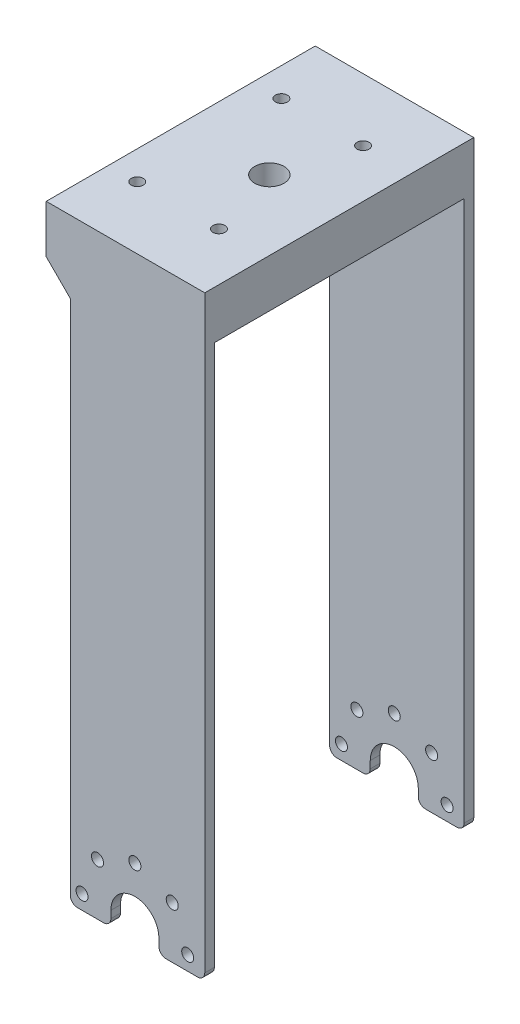
SolidWorks part; units mm, degrees
ref_plane "Front Plane" through (0, 0, 0) normal (0, 0, 1) x (1, 0, 0)
ref_plane "Top Plane" through (0, 0, 0) normal (0, 1, 0) x (1, 0, 0)
ref_plane "Right Plane" through (0, 0, 0) normal (1, 0, 0) x (0, 0, -1)
sketch "Sketch1" plane through (0, 0, 0) normal (0, 0, 1) x (1, 0, 0)
  line L1 (0, 0) -> (28, 0)
  line L2 (0, 0) -> (0, 124.1)
  line L3 (0, 124.1) -> (28, 124.1)
  line L4 (28, 0) -> (28, 124.1)
  dimension "D1" = 28
  dimension "D2" = 124.1
extrude "Boss-Extrude1" add sketch "Sketch1" against normal blind 2
ref_plane "Plane1" through (0, 0, -56) normal (0, 0, 1) x (1, 0, 0)
sketch "Sketch3" plane through (0, 0, 0) normal (0, 0, 1) x (1, 0, 0)
  line L0 (0, 0) -> (28, 0) construction
  line L2 (8.45, 3) -> (8.45, 0)
  line L3 (18.45, 3) -> (18.45, 0)
  arc A0 (18.45, 3) -> (8.45, 3) centre (13.45, 3) ccw
  dimension "D1" = 10
  dimension "D2" = 3
extrude "Cut-Extrude2" cut sketch "Sketch3" against normal blind 2 and the other way through all flip side to cut
ref_point "Point1"
ref_axis "Axis1" through (13.45, 3, 0) along (0, 0, -1)
sketch "Sketch4" plane through (0, 0, 0) normal (0, 0, 1) x (1, 0, 0)
  line L0 (0, 0) -> (8.45, 0) construction
  circle A0 centre (2.45, 3) radius 1.25
  arc A1 (18.45, 3) -> (8.45, 3) centre (13.45, 3) ccw construction
  dimension "D1" = 2.5
  dimension "D2" = 3
  dimension "D3" = 11
extrude "Cut-Extrude3" cut sketch "Sketch4" against normal blind 2
pattern_circular "CirPattern1" count 5 every 45 about axis through (13.45, 3, 0) along (0, 0, -1) of "Cut-Extrude3"
fillet "Fillet1" radius 1.5 4 edges at (28, 0, -1) (0, 0, -1) (18.45, 0, -1) (8.45, 0, -1)
sketch "Sketch7" plane through (0, 0, -56) normal (0, 0, 1) x (1, 0, 0)
  line L1 (0, 0) -> (28, 0)
  line L2 (0, 0) -> (0, 124.1)
  line L3 (0, 124.1) -> (28, 124.1)
  line L4 (28, 0) -> (28, 124.1)
  dimension "D1" = 28
  dimension "D2" = 124.1
extrude "Boss-Extrude2" add sketch "Sketch7" along normal blind 2 separate body
ref_point "Point2"
sketch "Sketch10" plane through (0, 0, -56) normal (0, 0, -1) x (-1, 0, 0)
  line L1 (-18.45, 3) -> (-18.45, 0)
  line L2 (0, 0) -> (-28, 0) construction
  line L3 (-8.45, 3) -> (-8.45, 0)
  arc A0 (-8.45, 3) -> (-18.45, 3) centre (-13.45, 3) ccw
  dimension "D1" = 10
extrude "Cut-Extrude4" cut sketch "Sketch10" against normal blind 2 and the other way through all flip side to cut
sketch "Sketch11" plane through (0, 0, -56) normal (0, 0, -1) x (-1, 0, 0)
  circle A0 centre (-24.45, 3) radius 1.25
  arc A1 (-8.45, 3) -> (-18.45, 3) centre (-13.45, 3) ccw construction
  dimension "D1" = 2.5
  dimension "D2" = 11
extrude "Cut-Extrude5" cut sketch "Sketch11" against normal blind 2
pattern_circular "CirPattern2" count 5 over 180 about axis through (13.45, 3, 0) along (0, 0, -1) of "Cut-Extrude5" reverse direction yes
fillet "Fillet2" radius 1.5 4 edges at (28, 0, -55) (0, 0, -55) (8.45, 0, -55) (18.45, 0, -55)
sketch "Sketch17" plane through (0, 124.1, 0) normal (0, 1, 0) x (1, 0, 0)
  line L1 (28, 2) -> (-5, 2)
  line L2 (28, 2) -> (28, 54)
  line L3 (28, 54) -> (-5, 54)
  line L4 (-5, 2) -> (-5, 54)
  dimension "D1" = 52
  dimension "D2" = 33
extrude "Boss-Extrude5" add sketch "Sketch17" against normal blind 15
sketch "Sketch18" plane through (0, 124.1, 0) normal (0, 1, 0) x (1, 0, 0)
  line L1 (-5, 2) -> (0, 2) construction
  circle A0 centre (13.45, 28) radius 3.05
  dimension "D1" = 6.1
  dimension "D2" = 26
extrude "Cut-Extrude7" cut sketch "Sketch18" against normal up to next
sketch "Sketch19" plane through (0, 124.1, 0) normal (0, 1, 0) x (1, 0, 0)
  circle A0 centre (0.95, 43) radius 1.25
  circle A1 centre (13.45, 28) radius 3.05 construction
  circle A2 centre (17.95, 43) radius 1.25
  dimension "D1" = 2.5
  dimension "D2" = 15
  dimension "D3" = 12.5
  dimension "D4" = 2.5
  dimension "D5" = 17
  dimension "D6" = 15
extrude "Cut-Extrude8" cut sketch "Sketch19" against normal blind 10
ref_plane "Plane4" through (0, 0, -28) normal (0, 0, -1) x (-1, 0, 0)
mirror "Mirror9" about plane through (0, 0, -28) normal (0, 0, -1) of "Cut-Extrude8"
sketch "Sketch20" plane through (0, 109.1, 0) normal (0, -1, 0) x (1, 0, 0)
  line L0 (28, -54) -> (0, -54) construction
  line L1 (26.05, -54) -> (-3.05, -54)
  line L2 (26.05, -54) -> (26.05, -2)
  line L3 (26.05, -2) -> (-3.05, -2)
  line L4 (-3.05, -54) -> (-3.05, -2)
  line L6 (28, -2) -> (28, -54) construction
  circle A1 centre (0.95, -43) radius 1.25 construction
  dimension "D1" = 52
  dimension "D2" = 1.95
  dimension "D3" = 4
extrude "Cut-Extrude9" cut sketch "Sketch20" against normal blind 5
sketch "Sketch21" plane through (0, 0, -2) normal (0, 0, 1) x (1, 0, 0)
  line L0 (0, 114.1) -> (0, 1.5) construction
  line L1 (-5, 124.1) -> (0, 124.1)
  line L2 (-5, 124.1) -> (-5, 109.1)
  line L3 (-5, 109.1) -> (0, 109.1)
  line L4 (0, 124.1) -> (0, 109.1)
extrude "Boss-Extrude6" add sketch "Sketch21" along normal blind 2
mirror "Mirror10" about plane through (0, 0, -28) normal (0, 0, -1) of "Boss-Extrude6"
sketch "Sketch22" plane through (26.05, 0, 0) normal (-1, 0, 0) x (0, 0, 1)
  line L0 (-54, 114.1) -> (-2, 114.1) construction
  line L1 (-2, 114.1) -> (-54, 114.1)
  line L2 (-2, 114.1) -> (-2, 109.1)
  line L3 (-2, 109.1) -> (-54, 109.1)
  line L4 (-54, 114.1) -> (-54, 109.1)
extrude "Cut-Extrude10" cut sketch "Sketch22" against normal through all
sketch "Sketch23" plane through (-3.05, 0, 0) normal (1, 0, 0) x (0, 0, -1)
  line L1 (2, 114.1) -> (54, 114.1)
  line L2 (2, 114.1) -> (2, 109.1)
  line L3 (2, 109.1) -> (54, 109.1)
  line L4 (54, 114.1) -> (54, 109.1)
extrude "Cut-Extrude11" cut sketch "Sketch23" against normal through all
sketch "Sketch24" plane through (0, 0, -2) normal (0, 0, -1) x (-1, 0, 0)
  line L0 (0, 109.1) -> (5, 114.1)
  line L1 (-28, 114.1) -> (5, 114.1) construction
  line L2 (5, 114.1) -> (5, 109.1)
  line L3 (5, 109.1) -> (0, 109.1) construction
  line L4 (5, 114.1) -> (5, 109.1) construction
  line L5 (5, 109.1) -> (0, 109.1)
extrude "Cut-Extrude12" cut sketch "Sketch24" against normal through all
mirror "Mirror11" about plane through (0, 0, -28) normal (0, 0, -1) of "Cut-Extrude12"
sketch "Sketch25" plane through (0, 114.1, 0) normal (0, -1, 0) x (1, 0, 0)
  circle A0 centre (0.95, -43) radius 2.5
  circle A1 centre (17.95, -43) radius 2.5
  dimension "D1" = 5
  dimension "D2" = 5
extrude "Cut-Extrude13" cut sketch "Sketch25" against normal blind 5
mirror "Mirror12" about plane through (0, 0, -28) normal (0, 0, -1) of "Cut-Extrude13"
